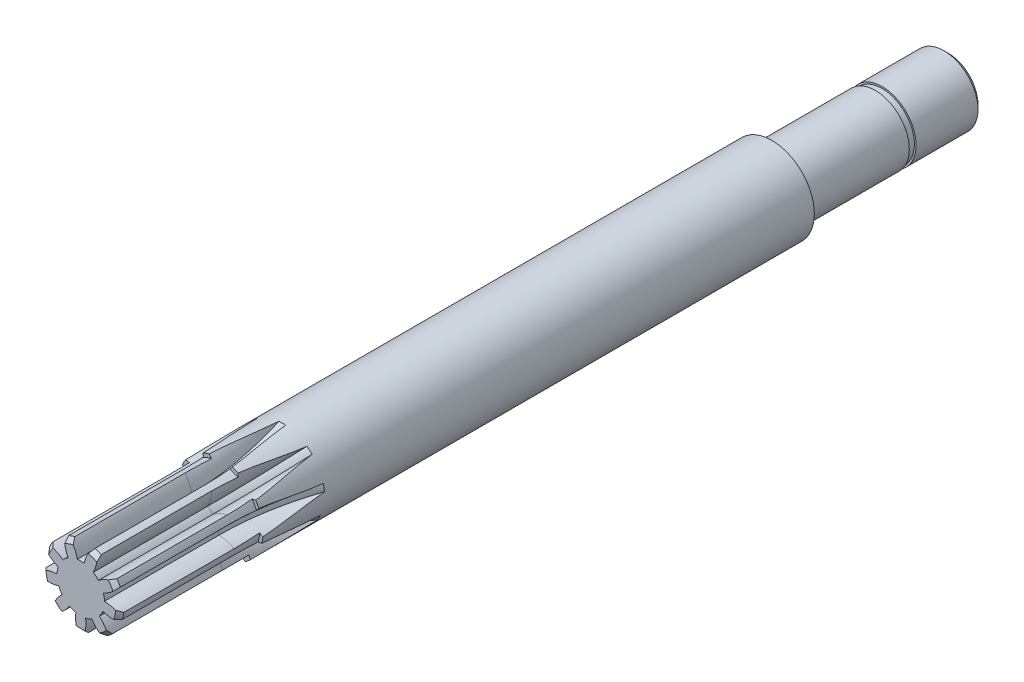
SolidWorks part; units mm, degrees
material "Acier allié"
ref_plane "Plan de face" through (0, 0, 0) normal (0, 0, 1) x (1, 0, 0)
ref_plane "Plan de dessus" through (0, 0, 0) normal (0, 1, 0) x (1, 0, 0)
ref_plane "Plan de droite" through (0, 0, 0) normal (1, 0, 0) x (0, 0, -1)
sketch "Esquisse1" plane through (0, 0, 0) normal (1, 0, 0) x (0, 0, -1)
  line L0 (-153.0128, 0) -> (21.5095, 0) construction
  line L1 (0, 5) -> (0, 4)
  line L2 (-81.5, 0) -> (20.8, 0)
  line L3 (-65, 4.6) -> (-65, 5)
  line L4 (-65, 5) -> (0, 5)
  line L5 (20.8, 0) -> (20.8, 3.5)
  line L6 (0, 4) -> (12.2, 4)
  line L7 (13, 4) -> (13, 3.8)
  line L8 (13, 3.8) -> (12.2, 3.8)
  line L9 (12.2, 3.8) -> (12.2, 4)
  line L10 (13, 4) -> (20.3, 4)
  line L11 (-81, 4.6) -> (-65, 4.6)
  line L12 (-81, 4.6) -> (-81.5, 4.1)
  line L14 (-81.5, 4.1) -> (-81.5, 0)
  line L15 (20.3, 4) -> (20.8, 3.5)
  point P2 (20, 4)
  dimension "D1" = 10
  dimension "D2" = 8
  dimension "D3" = 0.8
  dimension "D4" = 13
  dimension "D5" = 7.6
  dimension "D6" = 0.8
  dimension "D7" = 7
  dimension "D8" = 81.5
  dimension "D9" = 9.2
  dimension "D10" = 65
  dimension "D11" = 45
  dimension "D12" = 0.5
  dimension "D14" = 45
  dimension "D15" = 0.5
revolve "Révolution1" add sketch "Esquisse1" angle 360 about L0
ref_axis "Axe1" through (0, 0, 0) along (0, 0, 1)
sketch "Esquisse2" plane through (0, 0, 0) normal (1, 0, 0) x (0, 0, -1)
  line L0 (-104.47, 0) -> (-96.8975, 0) construction
  line L1 (-81.5, 2.8) -> (-68, 2.8)
  line L2 (-81.5, 4.1) -> (-81.5, -4.1) construction
  line L3 (0, -5) -> (0, 5) construction
  arc A0 (-68, 2.8) -> (-50.4455, 10) centre (-68, 27.8) ccw
  dimension "D3" = 25
  dimension "D1" = 5.6
  dimension "D2" = 68
  dimension "D4" = 10
sketch "Esquisse3" plane through (0, 0, 81.5) normal (0, 0, 1) x (1, 0, 0)
  line L0 (0, 0) -> (-1.5733, 4.3226) construction
  line L1 (0, 0) -> (0, 7.1418) construction
  line L2 (0, 2.8) -> (0, 10) construction
  line L3 (0, 0) -> (1.5733, 4.3226) construction
  line L4 (-2, 6) -> (2, 6)
  line L5 (-2, 5.1898) -> (-2, 6)
  line L6 (2, 5.1898) -> (2, 6)
  arc A0 (0.3992, 2.7714) -> (-0.3992, 2.7714) centre (0, 0) ccw
  circle A1 centre (0, 0) radius 4.6 construction
  circle A2 centre (0, 0) radius 4.6 construction
  arc A3 (-2, 5.1898) -> (-0.3992, 2.7714) centre (-4.3082, 1.923) cw
  circle A4 centre (0, 0) radius 3.6 construction
  arc A5 (2, 5.1898) -> (0.3992, 2.7714) centre (4.3082, 1.923) ccw
  point P15 (-0.65, 3.5408)
  point P17 (-1.2, 4.4407)
  dimension "D1" = 20
  dimension "D2" = 7.2
  dimension "D8" = 4
  dimension "D3" = 20
  dimension "D4" = 1.3
  dimension "D5" = 2.4
  dimension "D6" = 4
  dimension "D7" = 6
sweep "Enlèvement de matière-Balayage1" cut profiles "Esquisse3" path "Esquisse2"
pattern_circular "Répétition circulaire1" count 9 over 360 about axis through (0, 0, 0) along (0, 0, 1) of "Enlèvement de matière-Balayage1"
